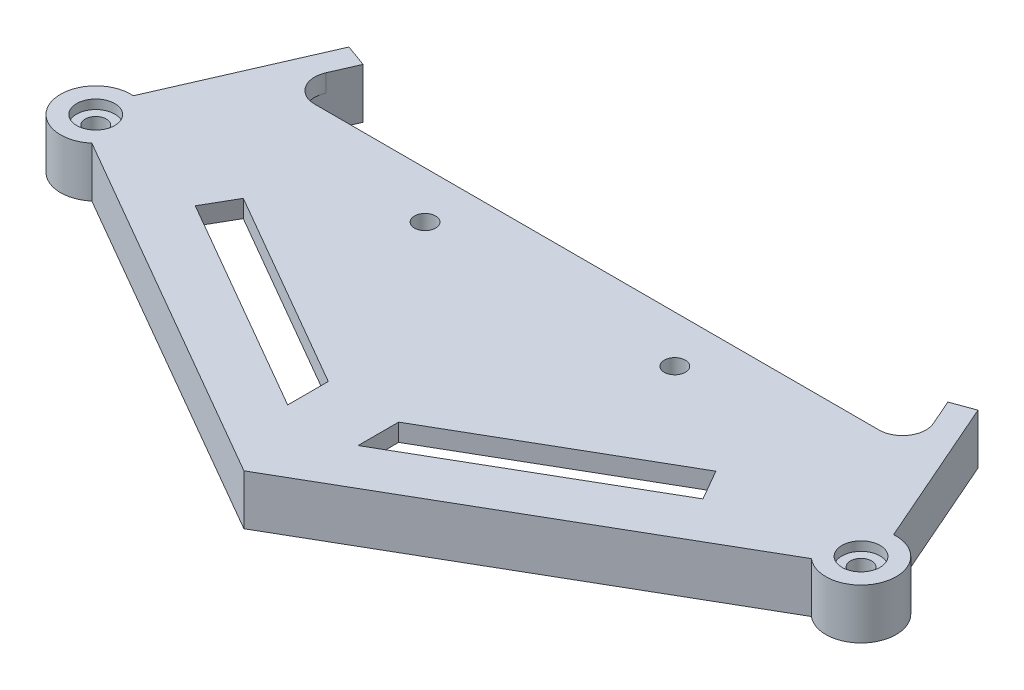
SolidWorks part; units mm, degrees
ref_plane "Front Plane" through (0, 0, 0) normal (0, 0, 1) x (1, 0, 0)
ref_plane "Top Plane" through (0, 0, 0) normal (0, 1, 0) x (1, 0, 0)
ref_plane "Right Plane" through (0, 0, 0) normal (1, 0, 0) x (0, 0, -1)
sketch "Sketch1" plane through (0, 0, 0) normal (0, 1, 0) x (1, 0, 0)
  line L0 (-2, 1.1547) -> (-61.3696, 35.4318)
  line L1 (-65.2686, 39.9923) -> (-42.6286, 26.921) construction
  line L2 (-2, 1.1547) -> (0, 0)
  line L3 (0, 4.6188) -> (-59.3696, 38.8959)
  line L4 (2, 1.1547) -> (0, 0)
  line L5 (2, 1.1547) -> (61.3696, 35.4318)
  line L6 (0, 4.6188) -> (59.3696, 38.8959)
  line L7 (-65.2686, 45.9923) -> (65.2686, 45.9923) construction
  line L8 (-65.2686, 39.9923) -> (-58.4065, 67.9795) construction
  line L9 (-58.4065, 67.9795) -> (-56.6964, 72.6779) construction
  line L10 (-56.6964, 72.6779) -> (-46.8296, 69.0867) construction
  line L11 (-46.8296, 69.0867) -> (-65.2686, 39.9923) construction
  line L12 (-51.763, 70.8823) -> (-65.2686, 39.9923) construction
  line L13 (-51.763, 70.8823) -> (-49.8799, 70.1969)
  line L14 (-49.8799, 70.1969) -> (-61.17, 44.3742)
  line L15 (-51.763, 70.8823) -> (-53.6461, 71.5677)
  line L16 (-53.6461, 71.5677) -> (-64.835, 45.9766)
  line L17 (0, 4.6188) -> (0, 66.7338) construction
  line L18 (49.8799, 70.1969) -> (61.17, 44.3742)
  line L19 (51.763, 70.8823) -> (49.8799, 70.1969)
  line L20 (51.763, 70.8823) -> (53.6461, 71.5677)
  line L21 (53.6461, 71.5677) -> (64.835, 45.9766)
  line L22 (-54.252, 60.1969) -> (54.252, 60.1969)
  line L23 (-49.8799, 70.1969) -> (49.8799, 70.1969) construction
  circle A0 centre (-65.2686, 39.9923) radius 6
  circle A1 centre (65.2686, 39.9923) radius 6
  circle A2 centre (-65.2686, 39.9923) radius 1.8
  circle A3 centre (65.2686, 39.9923) radius 1.8
  dimension "D1" = 12
  dimension "D7" = 3.6
  dimension "D8" = 3.6
  dimension "D2" = 2
  dimension "D3" = 68.5541
  dimension "D4" = 2.3094
  dimension "D5" = 68.5541
  dimension "D6" = 120
  dimension "D9" = 5
  dimension "D10" = 27.9872
  dimension "D11" = 34.4454
  dimension "D12" = 10.5
  dimension "D13" = 87.635
  dimension "D14" = 2
  dimension "D15" = 2
  dimension "D16" = 10
extrude "Boss-Extrude1" add sketch "Sketch1" along normal blind 4 contours A2 A0 | A1 L6 L3 A0 L0 L2 L4 L5 | A1 A3 | A1 L7 A0 L3 L6 | A0 L14 L13 L15 L16 | A1 L21 L20 L19 L18 region at (-31.041, 0, -19.4083) region at (-70.8075, 0, -38.172) region at (-57.3339, 0, -58.133) region at (0, 0, -39.497) region at (60.2194, 0, -37.0771) region at (57.3339, 0, -58.133)
fillet "Fillet1" radius 4 2 edges at (54.252, 2, -60.1969) (-54.252, 2, -60.1969)
sketch "Sketch2" plane through (0, 4, 0) normal (0, 1, 0) x (1, 0, 0)
  line L0 (-65.2686, 45.9923) -> (65.2686, 45.9923)
  line L4 (61.3696, 35.4318) -> (0, 0) construction
  line L5 (-61.3696, 35.4318) -> (0, 0)
  line L6 (0, 0) -> (61.3696, 35.4318)
  arc A0 (-64.835, 45.9766) -> (-61.3696, 35.4318) centre (-65.2686, 39.9923) ccw construction
  arc A1 (61.3696, 35.4318) -> (64.835, 45.9766) centre (65.2686, 39.9923) ccw construction
  arc A4 (65.2686, 45.9923) -> (61.3696, 35.4318) centre (65.2686, 39.9923) cw
  arc A5 (-65.2686, 45.9923) -> (-61.3696, 35.4318) centre (-65.2686, 39.9923) ccw
  circle A6 centre (-65.2686, 39.9923) radius 1.8
  circle A7 centre (65.2686, 39.9923) radius 1.8
extrude "Boss-Extrude2" [suppressed] add sketch "Sketch2" along normal blind 3 separate body
sketch "Sketch3" plane through (0, 0, 0) normal (0, -1, 0) x (1, 0, 0)
  circle A0 centre (-65.2686, -39.9923) radius 6
  circle A1 centre (65.2686, -39.9923) radius 6
extrude "Cut-Extrude1" [suppressed] cut sketch "Sketch3" against normal up to next
sketch "Sketch4" plane through (0, 4, 0) normal (0, 1, 0) x (1, 0, 0)
  line L5 (43.3013, 35) -> (40.3013, 40.1962)
  line L6 (40.3013, 40.1962) -> (0, 16.9282)
  line L7 (0, 10) -> (43.3013, 35)
  line L8 (-2, 1.1547) -> (-61.3696, 35.4318) construction
  line L15 (61.3696, 35.4318) -> (57.9342, 41.3821) construction
  line L16 (0, 0) -> (0, 10) construction
  line L17 (-43.3013, 35) -> (-40.3013, 40.1962)
  line L18 (0, 10) -> (-43.3013, 35)
  line L19 (-40.3013, 40.1962) -> (0, 16.9282)
  line L22 (0, 16.9282) -> (0, 45.9923) construction
  line L23 (-6, 20.3923) -> (-6, 13.4641)
  line L24 (6, 20.3923) -> (6, 13.4641)
  line L25 (2, 1.1547) -> (61.3696, 35.4318) construction
  dimension "D1" = 50
  dimension "D2" = 50
  dimension "D3" = 6
  dimension "D4" = 6
  dimension "D5" = 10
extrude "Cut-Extrude2" cut sketch "Sketch4" against normal up to next contours L7 L5 | L23 L19 L17 L18 region at (23.9111, 4, -27.2208) region at (-23.9111, 4, -27.2208)
sketch "Sketch5" plane through (0, 0, 0) normal (0, -1, 0) x (1, 0, 0)
  line L0 (-59.3696, -38.8959) -> (0, -4.6188)
  line L1 (0, -4.6188) -> (59.3696, -38.8959)
  line L2 (-61.3696, -35.4318) -> (0, 0)
  line L3 (0, 0) -> (61.3696, -35.4318)
  line L4 (61.17, -44.3742) -> (49.8799, -70.1969)
  line L5 (49.8799, -70.1969) -> (53.6461, -71.5677)
  line L6 (53.6461, -71.5677) -> (64.835, -45.9766)
  line L7 (-65.2686, -45.9923) -> (-53.6461, -71.5677)
  line L8 (-53.6461, -71.5677) -> (-49.8799, -70.1969)
  line L9 (-49.8799, -70.1969) -> (-61.17, -44.3742)
  arc A0 (59.3696, -38.8959) -> (61.3696, -35.4318) centre (65.2686, -39.9923) cw
  arc A1 (-61.3696, -35.4318) -> (-59.3696, -38.8959) centre (-65.2686, -39.9923) cw
  circle A2 centre (-65.2686, -39.9923) radius 6 construction
  arc A3 (61.17, -44.3742) -> (65.2686, -45.9923) centre (65.2686, -39.9923) ccw
  arc A4 (-61.17, -44.3742) -> (-65.2686, -45.9923) centre (-65.2686, -39.9923) cw
  line M7 (61.3696, -35.4318) -> (0, 0)
  line M8 (0, 0) -> (-61.3696, -35.4318)
  line M26 (-64.835, -45.9766) -> (-53.6461, -71.5677)
  line M27 (-53.6461, -71.5677) -> (-49.8799, -70.1969)
  line M28 (-49.8799, -70.1969) -> (-51.8026, -65.7993)
  line M32 (51.8026, -65.7993) -> (49.8799, -70.1969)
  line M33 (49.8799, -70.1969) -> (53.6461, -71.5677)
  line M34 (53.6461, -71.5677) -> (64.835, -45.9766)
extrude "Boss-Extrude3" add sketch "Sketch5" along normal blind 5.558 contours L9 A4 M26 M27 M28 | A1 L0 L1 A0 M8 M7 | A3 L4 M32 M33 M34 region at (-58.9574, 0, -36.3485) region at (57.3339, 0, -58.133) region at (-57.3339, 0, -58.133)
sketch "Sketch6" plane through (0, 0, 0) normal (0, -1, 0) x (1, 0, 0)
  line L0 (-21.3, -52.1969) -> (21.3, -52.1969) construction
  line L1 (-65.2686, -45.9923) -> (65.2686, -45.9923) construction
  line L2 (-54.252, -60.1969) -> (54.252, -60.1969) construction
  circle A0 centre (-21.3, -52.1969) radius 1.8
  circle A1 centre (21.3, -52.1969) radius 1.8
  point P4 (0, -52.1969)
  point P7 (0, -45.9923)
  dimension "D3" = 3.6
  dimension "D1" = 42.6
  dimension "D2" = 8
extrude "Cut-Extrude3" cut sketch "Sketch6" against normal through all contours A1 | A0 region at (21.3, 0, -52.1969)
ref_plane "Plane1" through (0, 0, 0) normal (0, 0, -1) x (-1, 0, 0)
sketch "Sketch16" plane through (0, 4, 0) normal (0, 1, 0) x (1, 0, 0)
  line L0 (-21.3, 52.1969) -> (-14.3, 35.6969) construction
  line L1 (-14.3, 35.6969) -> (14.3, 35.6969) construction
  line L2 (14.3, 35.6969) -> (21.3, 52.1969) construction
  line L3 (21.3, 52.1969) -> (-21.3, 52.1969) construction
  line L4 (14.4324, 35.4969) -> (28.523, 55.9969)
  line L5 (-14.4324, 35.4969) -> (14.4324, 35.4969)
  line L6 (28.523, 55.9969) -> (-28.523, 55.9969)
  line L7 (-21.4841, 52.1188) -> (-14.4324, 35.4969) construction
  line L8 (14.4324, 35.4969) -> (21.4841, 52.1188) construction
  line L9 (-28.523, 55.9969) -> (-14.4324, 35.4969)
  line L10 (-54.252, 60.1969) -> (54.252, 60.1969) construction
  line L11 (24.4316, 50.0444) -> (22.7834, 51.1773) construction
  line L12 (22.7834, 51.1773) -> (23.7836, 52.6325) construction
  circle A0 centre (-21.3, 52.1969) radius 1.8 construction
  circle A1 centre (21.3, 52.1969) radius 1.8 construction
  point P12 (-21.3, 53.9969)
  point P13 (21.3, 53.9969)
  dimension "D1" = 17.9234
  dimension "D2" = 28.6
  dimension "D3" = 17.9234
  dimension "D4" = 42.6
  dimension "D6" = 2
  dimension "D7" = 2
  dimension "D5" = 0.2
sketch "Sketch17" plane through (0, 0, 0) normal (0, -1, 0) x (1, 0, 0)
  circle A0 centre (65.2686, -39.9923) radius 1.8
  circle A1 centre (65.2686, -39.9923) radius 6
  circle A2 centre (-65.2686, -39.9923) radius 1.8
  circle A3 centre (-65.2686, -39.9923) radius 6
extrude "Boss-Extrude6" add sketch "Sketch17" along normal blind 0.56
sketch "Sketch18" plane through (0, 4, 0) normal (0, 1, 0) x (1, 0, 0)
  circle A0 centre (-65.2686, 39.9923) radius 1.8
  circle A1 centre (-65.2686, 39.9923) radius 6
  circle A2 centre (65.2686, 39.9923) radius 1.8
  circle A3 centre (65.2686, 39.9923) radius 6
extrude "Cut-Extrude13" cut sketch "Sketch18" against normal blind 2.56
sketch "Sketch19" plane through (0, -0.56, 0) normal (0, -1, 0) x (1, 0, 0)
  circle A0 centre (-65.2686, -39.9923) radius 3.25
  circle A1 centre (-65.2686, -39.9923) radius 6
  circle A2 centre (65.2686, -39.9923) radius 3.25
  circle A3 centre (65.2686, -39.9923) radius 6
  dimension "D1" = 6.5
  dimension "D2" = 6.5
extrude "Boss-Extrude7" add sketch "Sketch19" along normal up to surface (4.998 mm away) up to face at (0, -5.558, -25.4885)
sketch "Sketch20" plane through (0, 1.44, 0) normal (0, 1, 0) x (1, 0, 0)
  circle A0 centre (-65.2686, 39.9923) radius 3.25
  circle A1 centre (-65.2686, 39.9923) radius 6
  circle A2 centre (65.2686, 39.9923) radius 3.25
  circle A3 centre (65.2686, 39.9923) radius 6
  dimension "D1" = 6.5
  dimension "D2" = 6.5
extrude "Boss-Extrude8" add sketch "Sketch20" along normal up to surface (2.56 mm away) up to face at (0, 4, -53.7445)
sketch "Sketch7" plane through (0, 0, 0) normal (0, 0, -1) x (-1, 0, 0)
  line L4 (-12, -22.0098) -> (12, -22.0098)
  line L5 (-12, -22.0098) -> (-12, 2.0098)
  line L6 (-12, 2.0098) -> (12, 2.0098)
  line L7 (12, -22.0098) -> (12, 2.0098)
  line L8 (-12, -22.0098) -> (12, 2.0098) construction
  line L9 (-12, 2.0098) -> (12, -22.0098) construction
  circle A1 centre (0, -10) radius 12 construction
  dimension "D1" = 24
  dimension "D2" = 14
extrude "Boss-Extrude4" [suppressed] add sketch "Sketch7" along normal blind 7 contours L5 A1 | L5 A1
sketch "Sketch8" [suppressed] plane through (0, 0, 0) normal (0, 0, 1) x (1, 0, 0)
  line L0 (12, 2.0098) -> (0, 2.0098) construction
  line L1 (9.8727, -10) -> (4.9363, -1.45)
  line L2 (4.9363, -1.45) -> (-4.9363, -1.45)
  line L3 (-4.9363, -1.45) -> (-9.8727, -10)
  line L4 (-9.8727, -10) -> (-4.9363, -18.55)
  line L5 (-4.9363, -18.55) -> (4.9363, -18.55)
  line L6 (4.9363, -18.55) -> (9.8727, -10)
  circle A0 centre (0, -10) radius 8.55 construction
  dimension "D1" = 14
  dimension "D2" = 17.1
extrude "Cut-Extrude5" [suppressed] cut sketch "Sketch8" against normal blind 4
sketch "Sketch9" [suppressed] plane through (0, 0, -4) normal (0, 0, 1) x (1, 0, 0)
  circle A0 centre (0, -10) radius 7.5
  dimension "D1" = 15
extrude "Cut-Extrude6" [suppressed] cut sketch "Sketch9" against normal blind 1000
sketch "Sketch10" plane through (0, 4, 0) normal (0, 1, 0) x (1, 0, 0)
  line L0 (-81.8328, 55.5934) -> (83.8701, 55.5934)
  line L1 (83.8701, 55.5934) -> (83.8701, -6.6584)
  line L2 (83.8701, -6.6584) -> (-81.8328, -5.8661)
  line L3 (-81.8328, -5.8661) -> (-81.8328, 55.5934)
extrude "Cut-Extrude7" [suppressed] cut sketch "Sketch10" against normal up to surface (1.9902 mm away)
sketch "Sketch11" [suppressed] plane through (0, 2.0098, 0) normal (0, 1, 0) x (1, 0, 0)
  line L0 (-2, 1.1547) -> (-61.3696, 35.4318) construction
  line L1 (-61.3696, 35.4318) -> (-12, 6.9282)
  line L2 (-12, 6.9282) -> (-12, 0)
  line L3 (2.2, 0) -> (-2.2, 0) construction
  line L4 (-12, 0) -> (12, 0)
  line L5 (12, 0) -> (12, 6.9282)
  line L6 (12, 6.9282) -> (12, 0) construction
  line L7 (12, 6.9282) -> (61.3696, 35.4318)
  line L8 (-65.2686, 45.9923) -> (65.2686, 45.9923)
  line L9 (2, 1.1547) -> (61.3696, 35.4318) construction
  line L10 (-43.6113, 40.1901) -> (-45.6113, 36.726)
  line L11 (-45.6113, 36.726) -> (0, 10.3923)
  line L12 (0, 10.3923) -> (45.6113, 36.726)
  line L13 (45.6113, 36.726) -> (43.6113, 40.1901)
  line L14 (43.6113, 40.1901) -> (0, 15.0111)
  line L15 (0, 15.0111) -> (-43.6113, 40.1901)
  line L16 (-45.6113, 36.726) -> (-4, 12.7017) construction
  arc A0 (-65.2686, 45.9923) -> (-61.3696, 35.4318) centre (-65.2686, 39.9923) ccw
  circle A1 centre (65.2686, 39.9923) radius 6 construction
  arc A2 (65.2686, 45.9923) -> (61.3696, 35.4318) centre (65.2686, 39.9923) cw
  arc A3 (61.3696, 35.4318) -> (64.835, 45.9766) centre (65.2686, 39.9923) ccw construction
  circle A4 centre (-65.2686, 39.9923) radius 1.8
  circle A5 centre (-21.3, 52.1969) radius 1.8
  circle A6 centre (21.3, 52.1969) radius 1.8
  circle A7 centre (65.2686, 39.9923) radius 1.8
  circle A8 centre (-65.2686, 39.9923) radius 1.8 construction
  circle A9 centre (-21.3, 52.1969) radius 1.8 construction
  circle A10 centre (21.3, 52.1969) radius 1.8 construction
  circle A13 centre (65.2686, 39.9923) radius 1.8 construction
sketch "Sketch12" [suppressed] plane through (0, 0, 0) normal (0, 0, 1) x (1, 0, 0)
  line L0 (0, 2.0098) -> (0, -21.9902)
  line L1 (-12, -21.9902) -> (12, -21.9902)
  line L2 (12, -22.0098) -> (12, 2.0098) construction
  line L3 (12, -21.9902) -> (12, -22.0098)
  line L4 (12, -22.0098) -> (-12, -22.0098)
  line L5 (-12, -22.0098) -> (-12, -21.9902)
  line L6 (0, 2.0098) -> (-43.6113, 2.0098) construction
  point P9 (0, -21.9902)
  line M8 (-12, -22.0098) -> (12, -22.0098)
  line M9 (12, -22.0098) -> (12, 2.0098)
  line M11 (-12, 2.0098) -> (-12, -22.0098)
  dimension "D1" = 24
extrude "Cut-Extrude8" [suppressed] cut sketch "Sketch12" against normal through all both and the other way through all contours L1 M11 M8 M9 | L1 L3 L4 L5
sketch "Sketch13" [suppressed] plane through (0, 0, 0) normal (0, 0, 1) x (1, 0, 0)
  line L0 (-12, -9.9902) -> (-12.1878, -9.9902)
  line L1 (-12, -21.9902) -> (-12, 2.0098) construction
  line L2 (-12.1878, -9.9902) -> (-6.091, -20.55)
  line L3 (-6.091, -20.55) -> (6.091, -20.55)
  line L4 (6.091, -20.55) -> (12.1878, -9.9902)
  line L5 (12.1878, -9.9902) -> (12, -9.9902)
  line L6 (12, -21.9902) -> (12, 2.0098) construction
  line L7 (-9.8727, -10) -> (-4.9363, -18.55) construction
  line L8 (4.9363, -18.55) -> (9.8727, -10) construction
  line L9 (-4.9363, -18.55) -> (4.9363, -18.55) construction
  line L10 (-9.8727, -10) -> (-4.9363, -18.55) construction
  line L11 (4.9363, -18.55) -> (9.8727, -10) construction
  line L12 (-12, -9.9902) -> (-12, -21.9902)
  line L13 (-12, -21.9902) -> (12, -21.9902)
  line L14 (12, -21.9902) -> (12, -9.9902)
  line M10 (-12, -21.9902) -> (12, -21.9902)
  line M11 (12, -21.9902) -> (12, 2.0098)
  line M13 (-12, 2.0098) -> (-12, -21.9902)
  dimension "D1" = 2
  dimension "D2" = 2
  dimension "D3" = 2
extrude "Cut-Extrude10" [suppressed] cut sketch "Sketch13" against normal up to surface and the other way through all contours L4 L3 L2 M13 M10 M11 up to face at (0, 2, -60.1969)
sketch "Sketch14" plane through (0, 0, 0) normal (0, -1, 0) x (1, 0, 0)
  circle A0 centre (-65.2686, -39.9923) radius 6
  circle A1 centre (-65.2686, -39.9923) radius 1.8
  circle A2 centre (65.2686, -39.9923) radius 1.8
  circle A3 centre (65.2686, -39.9923) radius 6
extrude "Boss-Extrude5" [suppressed] add sketch "Sketch14" along normal blind 2.56
sketch "Sketch15" [suppressed] plane through (0, 2.0098, 0) normal (0, 1, 0) x (1, 0, 0)
  circle A0 centre (-65.2686, 39.9923) radius 3.25
  circle A1 centre (65.2686, 39.9923) radius 3.25
  dimension "D1" = 6.5
extrude "Cut-Extrude11" [suppressed] cut sketch "Sketch15" against normal blind 2.57
sketch "Sketch21" plane through (0, 4, 0) normal (0, 1, 0) x (1, 0, 0)
  line L1 (-92.2075, 80.0884) -> (87.9344, 80.0884)
  line L2 (-92.2075, 80.0884) -> (-92.2075, -7.5087)
  line L3 (-92.2075, -7.5087) -> (87.9344, -7.5087)
  line L4 (87.9344, 80.0884) -> (87.9344, -7.5087)
extrude "Cut-Extrude14" cut sketch "Sketch21" against normal blind 1
